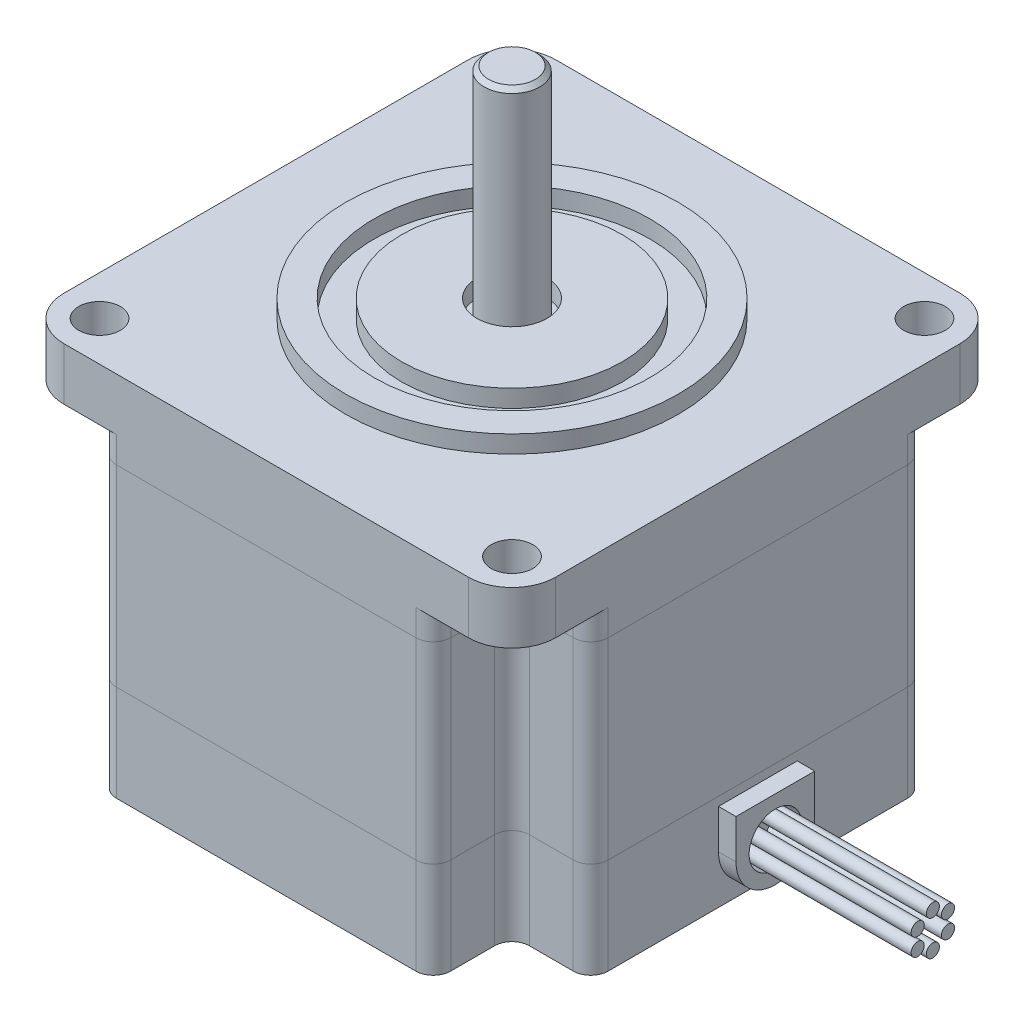
SolidWorks part; units mm, degrees
other "Camera1"
ref_plane "Front Plane" through (0, 0, 0) normal (0, 0, 1) x (1, 0, 0)
ref_plane "Top Plane" through (0, 0, 0) normal (0, 1, 0) x (1, 0, 0)
ref_plane "Right Plane" through (0, 0, 0) normal (1, 0, 0) x (0, 0, -1)
sketch "Sketch1" plane through (0, 0, 0) normal (0, 1, 0) x (1, 0, 0)
  line L1 (28.1, -28.1) -> (-28.1, -28.1)
  line L2 (28.1, -28.1) -> (28.1, 28.1)
  line L3 (28.1, 28.1) -> (-28.1, 28.1)
  line L4 (-28.1, -28.1) -> (-28.1, 28.1)
  line L5 (0, 28.1) -> (0, -28.1) construction
  line L6 (21, 0) -> (-28.1, 0) construction
  circle A0 centre (23.57, 23.57) radius 2.375
  circle A1 centre (23.57, -23.57) radius 2.375
  circle A2 centre (-23.57, -23.57) radius 2.375
  circle A3 centre (-23.57, 23.57) radius 2.375
  point P0 (0, 0)
  point P1 (-28.1, 28.1)
  point P6 (0, 28.1)
  point P7 (-28.1, 0)
  point P15 (0, 0)
  point P19 (0, -28.1)
  dimension "D2" = 4.75
  dimension "D1" = 56.2
  dimension "D4" = 47.14
  dimension "D3" = 4
extrude "Boss-Extrude2" add sketch "Sketch1" along normal blind 11
sketch "Sketch2" plane through (0, 11, 0) normal (0, 1, 0) x (1, 0, 0)
  line L8 (28.1, 28.1) -> (-28.1, 28.1)
  line L10 (-28.1, 28.1) -> (-28.1, -28.1)
  line L12 (-28.1, -28.1) -> (28.1, -28.1)
  line L14 (28.1, -28.1) -> (28.1, 28.1)
  line L16 (28.1, 28.1) -> (-28.1, 28.1)
  line L18 (-28.1, 28.1) -> (-28.1, -28.1)
  line L20 (-28.1, -28.1) -> (28.1, -28.1)
  line L22 (28.1, -28.1) -> (28.1, 28.1)
  circle A0 centre (-23.57, -23.57) radius 2.375 construction
  circle A1 centre (23.57, -23.57) radius 2.375 construction
  circle A2 centre (23.57, 23.57) radius 2.375 construction
  circle A3 centre (-23.57, 23.57) radius 2.375 construction
  circle A4 centre (-23.57, -23.57) radius 2.375
  circle A5 centre (23.57, -23.57) radius 2.375
  circle A6 centre (23.57, 23.57) radius 2.375
  circle A7 centre (-23.57, 23.57) radius 2.375
  dimension "D1" = 0
extrude "Boss-Extrude3" add sketch "Sketch2" along normal blind 22 separate body
sketch "Sketch3" plane through (0, 33, 0) normal (0, 1, 0) x (1, 0, 0)
  line L9 (28.1, 28.1) -> (-28.1, 28.1)
  line L11 (-28.1, 28.1) -> (-28.1, -28.1)
  line L13 (-28.1, -28.1) -> (28.1, -28.1)
  line L15 (28.1, -28.1) -> (28.1, 28.1)
  line L17 (28.1, 28.1) -> (-28.1, 28.1)
  line L19 (-28.1, 28.1) -> (-28.1, -28.1)
  line L21 (-28.1, -28.1) -> (28.1, -28.1)
  line L23 (28.1, -28.1) -> (28.1, 28.1)
  circle A0 centre (23.57, 23.57) radius 2.375 construction
  circle A1 centre (23.57, -23.57) radius 2.375 construction
  circle A2 centre (-23.57, -23.57) radius 2.375 construction
  circle A3 centre (-23.57, 23.57) radius 2.375 construction
  circle A4 centre (23.57, 23.57) radius 2.375
  circle A5 centre (23.57, -23.57) radius 2.375
  circle A6 centre (-23.57, -23.57) radius 2.375
  circle A7 centre (-23.57, 23.57) radius 2.375
  dimension "D1" = 0
extrude "Boss-Extrude4" add sketch "Sketch3" along normal blind 9 separate body
sketch "Sketch4" plane through (28.1, 0, 0) normal (1, 0, 0) x (0, 0, -1)
  line L1 (0, 0) -> (0, 11) construction
  line L2 (-28.1, 11) -> (28.1, 11) construction
  line L3 (-4.5, 5.5) -> (-4.5, 10)
  line L4 (-4.5, 10) -> (4.5, 10)
  line L5 (4.5, 5.5) -> (4.5, 10)
  arc A0 (-4.5, 5.5) -> (4.5, 5.5) centre (0, 5.5) ccw
  circle A1 centre (0, 5.5) radius 3
  point P11 (0, 10)
  dimension "D1" = 6
  dimension "D2" = 9
extrude "Boss-Extrude5" add sketch "Sketch4" along normal blind 2 separate body
sketch "Sketch5" plane through (28.1, 0, 0) normal (1, 0, 0) x (0, 0, -1)
  circle A0 centre (-1.7321, 4.5) radius 0.75
  circle A1 centre (0, 3.5) radius 0.75
  circle A2 centre (-1.7321, 6.5) radius 0.75
  circle A3 centre (0, 7.5) radius 0.75
  circle A4 centre (1.7321, 6.5) radius 0.75
  circle A5 centre (1.7321, 4.5) radius 0.75
  circle A6 centre (0, 5.5) radius 2 construction
  point P15 (0, 5.5)
  dimension "D1" = 1.5
  dimension "D3" = 4
  dimension "D2" = 6
extrude "Boss-Extrude6" add sketch "Sketch5" along normal blind 20 separate body contours A2 | A0 | A1 | A5 | A4 | A3
sketch "Sketch6" plane through (0, 42, 0) normal (0, 1, 0) x (1, 0, 0)
  circle A0 centre (0, 0) radius 12.6
  circle A1 centre (0, 0) radius 19
  circle A2 centre (0, 0) radius 15.75
  circle A3 centre (0, 0) radius 4
  dimension "D1" = 25.2
  dimension "D2" = 38
  dimension "D3" = 31.5
  dimension "D4" = 8
extrude "Boss-Extrude7" add sketch "Sketch6" along normal blind 2 contours A1 A2 | A0 region at (-12.2436, 42, 0) region at (-18.4626, 42, 0)
sketch "Sketch7" plane through (0, 42, 0) normal (0, 1, 0) x (1, 0, 0)
  circle A0 centre (0, 0) radius 3.175
  dimension "D1" = 6.35
extrude "Boss-Extrude8" add sketch "Sketch7" along normal blind 25 separate body
sketch "Sketch8" plane through (0, 67, 0) normal (0, 1, 0) x (1, 0, 0)
  circle A0 centre (0, 0) radius 7.675
  circle A1 centre (0, 0) radius 3.175
  circle A2 centre (0, 0) radius 3.175
  dimension "D2" = 15.35
  dimension "D1" = 0
extrude "Boss-Extrude9" [suppressed] add sketch "Sketch8" against normal blind 10 separate body
sketch "Sketch9" [suppressed] plane through (0, 56, 0) normal (0, -1, 0) x (1, 0, 0)
  circle A0 centre (0, 0) radius 10
  dimension "D1" = 20
extrude "Boss-Extrude10" [suppressed] add sketch "Sketch9" against normal blind 1
sketch "Sketch10" [suppressed] plane through (0, 66, 0) normal (0, 1, 0) x (1, 0, 0)
  line L0 (0, 7.675) -> (0, 8.675) construction
  line L1 (-0.6, 7.6515) -> (-0.3, 8.4658)
  line L2 (0.6, 7.6515) -> (0.3, 8.4658)
  line L3 (1.1177, 7.5932) -> (1.5913, 8.3203)
  line L4 (2.2876, 7.3262) -> (2.1763, 8.1868)
  line L5 (1.7078, 7.4826) -> (1.9304, 8.4575) construction
  line L6 (2.7793, 7.1541) -> (3.4029, 7.7576)
  line L7 (3.8604, 6.6334) -> (3.9435, 7.4973)
  line L8 (3.3301, 6.9149) -> (3.7639, 7.8159) construction
  line L9 (4.3015, 6.3563) -> (5.0438, 6.8059)
  line L10 (5.2397, 5.6081) -> (5.5129, 6.4318)
  line L11 (4.7853, 6.0006) -> (5.4088, 6.7824) construction
  line L12 (5.6081, 5.2397) -> (6.4318, 5.5129)
  line L13 (6.3563, 4.3015) -> (6.8059, 5.0438)
  line L14 (6.0006, 4.7853) -> (6.7824, 5.4088) construction
  line L15 (6.6334, 3.8604) -> (7.4973, 3.9435)
  line L16 (7.1541, 2.7793) -> (7.7576, 3.4029)
  line L17 (6.9149, 3.3301) -> (7.8159, 3.7639) construction
  line L18 (7.3262, 2.2876) -> (8.1868, 2.1763)
  line L19 (7.5932, 1.1177) -> (8.3203, 1.5913)
  line L20 (7.4826, 1.7078) -> (8.4575, 1.9304) construction
  line L21 (7.6515, 0.6) -> (8.4658, 0.3)
  line L22 (7.6515, -0.6) -> (8.4658, -0.3)
  line L23 (7.675, 0) -> (8.675, 0) construction
  line L24 (7.5932, -1.1177) -> (8.3203, -1.5913)
  line L25 (7.3262, -2.2876) -> (8.1868, -2.1763)
  line L26 (7.4826, -1.7078) -> (8.4575, -1.9304) construction
  line L27 (7.1541, -2.7793) -> (7.7576, -3.4029)
  line L28 (6.6334, -3.8604) -> (7.4973, -3.9435)
  line L29 (6.9149, -3.3301) -> (7.8159, -3.7639) construction
  line L30 (6.3563, -4.3015) -> (6.8059, -5.0438)
  line L31 (5.6081, -5.2397) -> (6.4318, -5.5129)
  line L32 (6.0006, -4.7853) -> (6.7824, -5.4088) construction
  line L33 (5.2397, -5.6081) -> (5.5129, -6.4318)
  line L34 (4.3015, -6.3563) -> (5.0438, -6.8059)
  line L35 (4.7853, -6.0006) -> (5.4088, -6.7824) construction
  line L36 (3.8604, -6.6334) -> (3.9435, -7.4973)
  line L37 (2.7793, -7.1541) -> (3.4029, -7.7576)
  line L38 (3.3301, -6.9149) -> (3.7639, -7.8159) construction
  line L39 (2.2876, -7.3262) -> (2.1763, -8.1868)
  line L40 (1.1177, -7.5932) -> (1.5913, -8.3203)
  line L41 (1.7078, -7.4826) -> (1.9304, -8.4575) construction
  line L42 (0.6, -7.6515) -> (0.3, -8.4658)
  line L43 (-0.6, -7.6515) -> (-0.3, -8.4658)
  line L44 (0, -7.675) -> (0, -8.675) construction
  line L45 (-1.1177, -7.5932) -> (-1.5913, -8.3203)
  line L46 (-2.2876, -7.3262) -> (-2.1763, -8.1868)
  line L47 (-1.7078, -7.4826) -> (-1.9304, -8.4575) construction
  line L48 (-2.7793, -7.1541) -> (-3.4029, -7.7576)
  line L49 (-3.8604, -6.6334) -> (-3.9435, -7.4973)
  line L50 (-3.3301, -6.9149) -> (-3.7639, -7.8159) construction
  line L51 (-4.3015, -6.3563) -> (-5.0438, -6.8059)
  line L52 (-5.2397, -5.6081) -> (-5.5129, -6.4318)
  line L53 (-4.7853, -6.0006) -> (-5.4088, -6.7824) construction
  line L54 (-5.6081, -5.2397) -> (-6.4318, -5.5129)
  line L55 (-6.3563, -4.3015) -> (-6.8059, -5.0438)
  line L56 (-6.0006, -4.7853) -> (-6.7824, -5.4088) construction
  line L57 (-6.6334, -3.8604) -> (-7.4973, -3.9435)
  line L58 (-7.1541, -2.7793) -> (-7.7576, -3.4029)
  line L59 (-6.9149, -3.3301) -> (-7.8159, -3.7639) construction
  line L60 (-7.3262, -2.2876) -> (-8.1868, -2.1763)
  line L61 (-7.5932, -1.1177) -> (-8.3203, -1.5913)
  line L62 (-7.4826, -1.7078) -> (-8.4575, -1.9304) construction
  line L63 (-7.6515, -0.6) -> (-8.4658, -0.3)
  line L64 (-7.6515, 0.6) -> (-8.4658, 0.3)
  line L65 (-7.675, 0) -> (-8.675, 0) construction
  line L66 (-7.5932, 1.1177) -> (-8.3203, 1.5913)
  line L67 (-7.3262, 2.2876) -> (-8.1868, 2.1763)
  line L68 (-7.4826, 1.7078) -> (-8.4575, 1.9304) construction
  line L69 (-7.1541, 2.7793) -> (-7.7576, 3.4029)
  line L70 (-6.6334, 3.8604) -> (-7.4973, 3.9435)
  line L71 (-6.9149, 3.3301) -> (-7.8159, 3.7639) construction
  line L72 (-6.3563, 4.3015) -> (-6.8059, 5.0438)
  line L73 (-5.6081, 5.2397) -> (-6.4318, 5.5129)
  line L74 (-6.0006, 4.7853) -> (-6.7824, 5.4088) construction
  line L75 (-5.2397, 5.6081) -> (-5.5129, 6.4318)
  line L76 (-4.3015, 6.3563) -> (-5.0438, 6.8059)
  line L77 (-4.7853, 6.0006) -> (-5.4088, 6.7824) construction
  line L78 (-3.8604, 6.6334) -> (-3.9435, 7.4973)
  line L79 (-2.7793, 7.1541) -> (-3.4029, 7.7576)
  line L80 (-3.3301, 6.9149) -> (-3.7639, 7.8159) construction
  line L81 (-2.2876, 7.3262) -> (-2.1763, 8.1868)
  line L82 (-1.1177, 7.5932) -> (-1.5913, 8.3203)
  line L83 (-1.7078, 7.4826) -> (-1.9304, 8.4575) construction
  circle A0 centre (0, 0) radius 8.675 construction
  circle A1 centre (0, 0) radius 7.675 construction
  circle A2 centre (0, 0) radius 7.675 construction
  arc A3 (-0.3, 8.4658) -> (0, 8.675) centre (0, 8.3553) cw
  circle A4 centre (0, 0) radius 7.675
  arc A5 (0.6, 7.6515) -> (-0.6, 7.6515) centre (0, 0) ccw
  arc A6 (0.3, 8.4658) -> (0, 8.675) centre (0, 8.3553) ccw
  arc A7 (1.5913, 8.3203) -> (1.9304, 8.4575) centre (1.8592, 8.1458) cw
  arc A8 (2.2876, 7.3262) -> (1.1177, 7.5932) centre (0, 0) ccw
  arc A9 (2.1763, 8.1868) -> (1.9304, 8.4575) centre (1.8592, 8.1458) ccw
  arc A10 (3.4029, 7.7576) -> (3.7639, 7.8159) centre (3.6252, 7.5279) cw
  arc A11 (3.8604, 6.6334) -> (2.7793, 7.1541) centre (0, 0) ccw
  arc A12 (3.9435, 7.4973) -> (3.7639, 7.8159) centre (3.6252, 7.5279) ccw
  arc A13 (5.0438, 6.8059) -> (5.4088, 6.7824) centre (5.2094, 6.5324) cw
  arc A14 (5.2397, 5.6081) -> (4.3015, 6.3563) centre (0, 0) ccw
  arc A15 (5.5129, 6.4318) -> (5.4088, 6.7824) centre (5.2094, 6.5324) ccw
  arc A16 (6.4318, 5.5129) -> (6.7824, 5.4088) centre (6.5324, 5.2094) cw
  arc A17 (6.3563, 4.3015) -> (5.6081, 5.2397) centre (0, 0) ccw
  arc A18 (6.8059, 5.0438) -> (6.7824, 5.4088) centre (6.5324, 5.2094) ccw
  arc A19 (7.4973, 3.9435) -> (7.8159, 3.7639) centre (7.5279, 3.6252) cw
  arc A20 (7.1541, 2.7793) -> (6.6334, 3.8604) centre (0, 0) ccw
  arc A21 (7.7576, 3.4029) -> (7.8159, 3.7639) centre (7.5279, 3.6252) ccw
  arc A22 (8.1868, 2.1763) -> (8.4575, 1.9304) centre (8.1458, 1.8592) cw
  arc A23 (7.5932, 1.1177) -> (7.3262, 2.2876) centre (0, 0) ccw
  arc A24 (8.3203, 1.5913) -> (8.4575, 1.9304) centre (8.1458, 1.8592) ccw
  arc A25 (8.4658, 0.3) -> (8.675, 0) centre (8.3553, 0) cw
  arc A26 (7.6515, -0.6) -> (7.6515, 0.6) centre (0, 0) ccw
  arc A27 (8.4658, -0.3) -> (8.675, 0) centre (8.3553, 0) ccw
  arc A28 (8.3203, -1.5913) -> (8.4575, -1.9304) centre (8.1458, -1.8592) cw
  arc A29 (7.3262, -2.2876) -> (7.5932, -1.1177) centre (0, 0) ccw
  arc A30 (8.1868, -2.1763) -> (8.4575, -1.9304) centre (8.1458, -1.8592) ccw
  arc A31 (7.7576, -3.4029) -> (7.8159, -3.7639) centre (7.5279, -3.6252) cw
  arc A32 (6.6334, -3.8604) -> (7.1541, -2.7793) centre (0, 0) ccw
  arc A33 (7.4973, -3.9435) -> (7.8159, -3.7639) centre (7.5279, -3.6252) ccw
  arc A34 (6.8059, -5.0438) -> (6.7824, -5.4088) centre (6.5324, -5.2094) cw
  arc A35 (5.6081, -5.2397) -> (6.3563, -4.3015) centre (0, 0) ccw
  arc A36 (6.4318, -5.5129) -> (6.7824, -5.4088) centre (6.5324, -5.2094) ccw
  arc A37 (5.5129, -6.4318) -> (5.4088, -6.7824) centre (5.2094, -6.5324) cw
  arc A38 (4.3015, -6.3563) -> (5.2397, -5.6081) centre (0, 0) ccw
  arc A39 (5.0438, -6.8059) -> (5.4088, -6.7824) centre (5.2094, -6.5324) ccw
  arc A40 (3.9435, -7.4973) -> (3.7639, -7.8159) centre (3.6252, -7.5279) cw
  arc A41 (2.7793, -7.1541) -> (3.8604, -6.6334) centre (0, 0) ccw
  arc A42 (3.4029, -7.7576) -> (3.7639, -7.8159) centre (3.6252, -7.5279) ccw
  arc A43 (2.1763, -8.1868) -> (1.9304, -8.4575) centre (1.8592, -8.1458) cw
  arc A44 (1.1177, -7.5932) -> (2.2876, -7.3262) centre (0, 0) ccw
  arc A45 (1.5913, -8.3203) -> (1.9304, -8.4575) centre (1.8592, -8.1458) ccw
  arc A46 (0.3, -8.4658) -> (0, -8.675) centre (0, -8.3553) cw
  arc A47 (-0.6, -7.6515) -> (0.6, -7.6515) centre (0, 0) ccw
  arc A48 (-0.3, -8.4658) -> (0, -8.675) centre (0, -8.3553) ccw
  arc A49 (-1.5913, -8.3203) -> (-1.9304, -8.4575) centre (-1.8592, -8.1458) cw
  arc A50 (-2.2876, -7.3262) -> (-1.1177, -7.5932) centre (0, 0) ccw
  arc A51 (-2.1763, -8.1868) -> (-1.9304, -8.4575) centre (-1.8592, -8.1458) ccw
  arc A52 (-3.4029, -7.7576) -> (-3.7639, -7.8159) centre (-3.6252, -7.5279) cw
  arc A53 (-3.8604, -6.6334) -> (-2.7793, -7.1541) centre (0, 0) ccw
  arc A54 (-3.9435, -7.4973) -> (-3.7639, -7.8159) centre (-3.6252, -7.5279) ccw
  arc A55 (-5.0438, -6.8059) -> (-5.4088, -6.7824) centre (-5.2094, -6.5324) cw
  arc A56 (-5.2397, -5.6081) -> (-4.3015, -6.3563) centre (0, 0) ccw
  arc A57 (-5.5129, -6.4318) -> (-5.4088, -6.7824) centre (-5.2094, -6.5324) ccw
  arc A58 (-6.4318, -5.5129) -> (-6.7824, -5.4088) centre (-6.5324, -5.2094) cw
  arc A59 (-6.3563, -4.3015) -> (-5.6081, -5.2397) centre (0, 0) ccw
  arc A60 (-6.8059, -5.0438) -> (-6.7824, -5.4088) centre (-6.5324, -5.2094) ccw
  arc A61 (-7.4973, -3.9435) -> (-7.8159, -3.7639) centre (-7.5279, -3.6252) cw
  arc A62 (-7.1541, -2.7793) -> (-6.6334, -3.8604) centre (0, 0) ccw
  arc A63 (-7.7576, -3.4029) -> (-7.8159, -3.7639) centre (-7.5279, -3.6252) ccw
  arc A64 (-8.1868, -2.1763) -> (-8.4575, -1.9304) centre (-8.1458, -1.8592) cw
  arc A65 (-7.5932, -1.1177) -> (-7.3262, -2.2876) centre (0, 0) ccw
  arc A66 (-8.3203, -1.5913) -> (-8.4575, -1.9304) centre (-8.1458, -1.8592) ccw
  arc A67 (-8.4658, -0.3) -> (-8.675, 0) centre (-8.3553, 0) cw
  arc A68 (-7.6515, 0.6) -> (-7.6515, -0.6) centre (0, 0) ccw
  arc A69 (-8.4658, 0.3) -> (-8.675, 0) centre (-8.3553, 0) ccw
  arc A70 (-8.3203, 1.5913) -> (-8.4575, 1.9304) centre (-8.1458, 1.8592) cw
  arc A71 (-7.3262, 2.2876) -> (-7.5932, 1.1177) centre (0, 0) ccw
  arc A72 (-8.1868, 2.1763) -> (-8.4575, 1.9304) centre (-8.1458, 1.8592) ccw
  arc A73 (-7.7576, 3.4029) -> (-7.8159, 3.7639) centre (-7.5279, 3.6252) cw
  arc A74 (-6.6334, 3.8604) -> (-7.1541, 2.7793) centre (0, 0) ccw
  arc A75 (-7.4973, 3.9435) -> (-7.8159, 3.7639) centre (-7.5279, 3.6252) ccw
  arc A76 (-6.8059, 5.0438) -> (-6.7824, 5.4088) centre (-6.5324, 5.2094) cw
  arc A77 (-5.6081, 5.2397) -> (-6.3563, 4.3015) centre (0, 0) ccw
  arc A78 (-6.4318, 5.5129) -> (-6.7824, 5.4088) centre (-6.5324, 5.2094) ccw
  arc A79 (-5.5129, 6.4318) -> (-5.4088, 6.7824) centre (-5.2094, 6.5324) cw
  arc A80 (-4.3015, 6.3563) -> (-5.2397, 5.6081) centre (0, 0) ccw
  arc A81 (-5.0438, 6.8059) -> (-5.4088, 6.7824) centre (-5.2094, 6.5324) ccw
  arc A82 (-3.9435, 7.4973) -> (-3.7639, 7.8159) centre (-3.6252, 7.5279) cw
  arc A83 (-2.7793, 7.1541) -> (-3.8604, 6.6334) centre (0, 0) ccw
  arc A84 (-3.4029, 7.7576) -> (-3.7639, 7.8159) centre (-3.6252, 7.5279) ccw
  arc A85 (-2.1763, 8.1868) -> (-1.9304, 8.4575) centre (-1.8592, 8.1458) cw
  arc A86 (-1.1177, 7.5932) -> (-2.2876, 7.3262) centre (0, 0) ccw
  arc A87 (-1.5913, 8.3203) -> (-1.9304, 8.4575) centre (-1.8592, 8.1458) ccw
  point P236 (0, 0)
  dimension "D1" = 17.35
  dimension "D2" = 0
  dimension "D3" = 1.2
  dimension "D5" = 0.6
  dimension "D4" = 28
extrude "Boss-Extrude12" [suppressed] add sketch "Sketch10" against normal blind 9
sketch "Sketch11" plane through (0, 0, 0) normal (0, -1, 0) x (1, 0, 0)
  line L0 (0, 21.8817) -> (0, 0) construction
  line L2 (0, 0) -> (43.9252, 0) construction
  line L4 (28.1, 23.6) -> (19.1, 23.6) construction
  line L5 (-28.1, 28.1) -> (-19.1, 28.1)
  line L6 (-28.1, 28.1) -> (-28.1, 19.1)
  line L7 (-28.1, 19.1) -> (-19.1, 19.1)
  line L8 (-19.1, 28.1) -> (-19.1, 19.1)
  line L9 (-23.6, 19.1) -> (-23.6, 28.1) construction
  line L10 (-28.1, 23.6) -> (-19.1, 23.6) construction
  line L11 (23.6, 19.1) -> (23.6, 28.1) construction
  line L12 (19.1, 28.1) -> (19.1, 19.1)
  line L13 (28.1, 19.1) -> (19.1, 19.1)
  line L14 (28.1, 28.1) -> (28.1, 19.1)
  line L15 (28.1, 28.1) -> (19.1, 28.1)
  line L16 (23.6, -19.1) -> (23.6, -28.1) construction
  line L17 (-28.1, -23.6) -> (-19.1, -23.6) construction
  line L18 (-23.6, -19.1) -> (-23.6, -28.1) construction
  line L19 (28.1, -23.6) -> (19.1, -23.6) construction
  line L20 (28.1, -28.1) -> (19.1, -28.1)
  line L21 (28.1, -28.1) -> (28.1, -19.1)
  line L22 (28.1, -19.1) -> (19.1, -19.1)
  line L23 (19.1, -28.1) -> (19.1, -19.1)
  line L24 (-19.1, -28.1) -> (-19.1, -19.1)
  line L25 (-28.1, -19.1) -> (-19.1, -19.1)
  line L26 (-28.1, -28.1) -> (-28.1, -19.1)
  line L27 (-28.1, -28.1) -> (-19.1, -28.1)
  point P20 (23.6, 23.6)
  point P38 (-23.6, -23.6)
  point P39 (23.6, -23.6)
  point P52 (-23.6, 23.6)
  dimension "D1" = 9
extrude "Cut-Extrude1" cut sketch "Sketch11" against normal offset from surface (36 mm away) 6 up to face at (0, 42, 19)
fillet "Fillet1" radius 5 4 edges at (-28.1, 39, 28.1) (28.1, 39, 28.1) (28.1, 39, -28.1) (-28.1, 39, -28.1)
fillet "Fillet2" radius 2 12 edges at (19.1, 5.5, -28.1) (19.1, 5.5, -19.1) (28.1, 5.5, -19.1) (-28.1, 5.5, -19.1) (-19.1, 5.5, -19.1) (-19.1, 5.5, -28.1) (-28.1, 5.5, 19.1) (-19.1, 5.5, 19.1) (-19.1, 5.5, 28.1) (28.1, 5.5, 19.1) (19.1, 5.5, 28.1) (19.1, 5.5, 19.1)
fillet "Fillet3" radius 2 12 edges at (28.1, 22, 19.1) (19.1, 22, 19.1) (19.1, 22, 28.1) (-19.1, 22, 28.1) (-19.1, 22, 19.1) (-28.1, 22, 19.1) (-28.1, 22, -19.1) (-19.1, 22, -19.1) (-19.1, 22, -28.1) (19.1, 22, -28.1) (28.1, 22, -19.1) (19.1, 22, -19.1)
chamfer "Chamfer1" distance 0.5 angle 45 1 edges at (0, 67, 3.175)
fillet "Fillet4" radius 2 12 edges at (19.1, 34.5, -28.1) (28.1, 34.5, -19.1) (19.1, 34.5, -19.1) (-19.1, 34.5, -28.1) (-19.1, 34.5, -19.1) (-28.1, 34.5, -19.1) (-28.1, 34.5, 19.1) (-19.1, 34.5, 19.1) (-19.1, 34.5, 28.1) (28.1, 34.5, 19.1) (19.1, 34.5, 19.1) (19.1, 34.5, 28.1)
